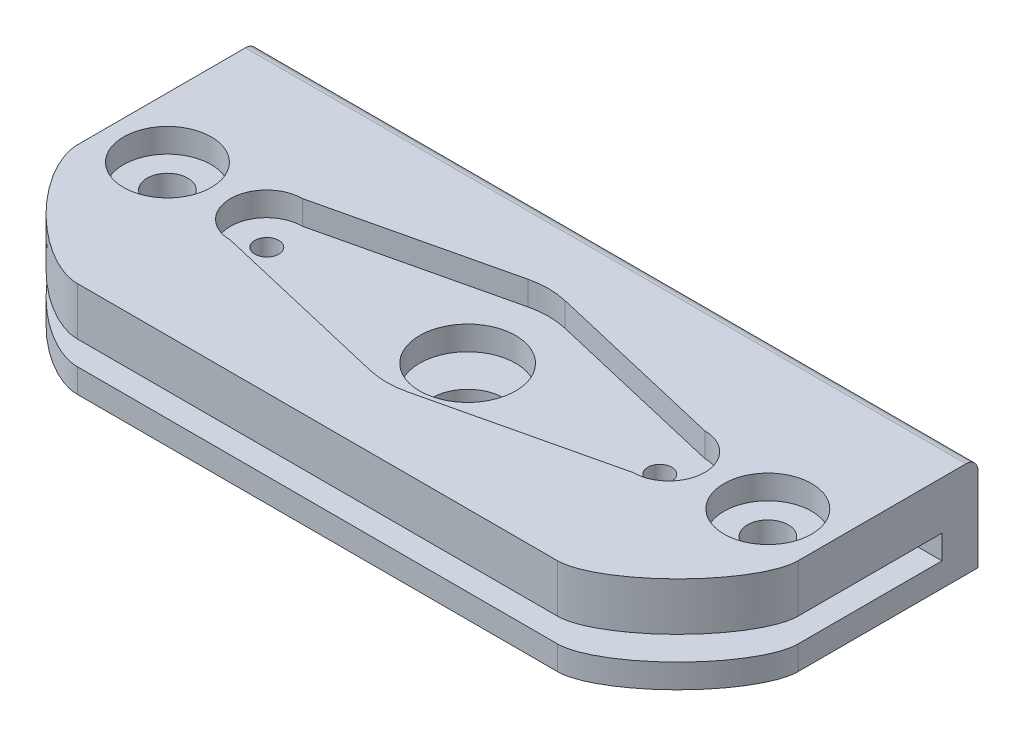
SolidWorks part; units mm, degrees
ref_plane "Front Plane" through (0, 0, 0) normal (0, 0, 1) x (1, 0, 0)
ref_plane "Top Plane" through (0, 0, 0) normal (0, 1, 0) x (1, 0, 0)
ref_plane "Right Plane" through (0, 0, 0) normal (1, 0, 0) x (0, 0, -1)
sketch "Sketch1" plane through (0, 0, 0) normal (0, 0, 1) x (1, 0, 0)
  line L1 (-20.0715, -2.0352) -> (39.9285, -2.0352)
  line L2 (-20.0715, -2.0352) -> (-20.0715, -10.0352)
  line L3 (-20.0715, -10.0352) -> (39.9285, -10.0352)
  line L4 (39.9285, -2.0352) -> (39.9285, -10.0352)
extrude "Boss-Extrude1" add sketch "Sketch1" along normal blind 25
sketch "Sketch2" plane through (0, 0, 25) normal (0, 0, 1) x (1, 0, 0)
  line L0 (-20.0715, -6.0352) -> (-20.0715, -8.0352)
  line L1 (-20.0715, -2.0352) -> (-20.0715, -10.0352) construction
  line L2 (-20.0715, -8.0352) -> (39.9285, -8.0352)
  line L3 (39.9285, -10.0352) -> (39.9285, -2.0352) construction
  line L4 (39.9285, -8.0352) -> (39.9285, -6.0352)
  line L5 (39.9285, -6.0352) -> (-20.0715, -6.0352)
extrude "Cut-Extrude1" cut sketch "Sketch2" against normal blind 22
sketch "Sketch3" plane through (0, -2.0352, 0) normal (0, 1, 0) x (1, 0, 0)
  line L3 (26.6785, -9.5) -> (11.4717, -5.9288)
  line L4 (-6.8215, -9.5) -> (8.3853, -5.9288)
  line L5 (-6.8215, -15.5) -> (8.3853, -19.0712)
  line L6 (26.6785, -15.5) -> (11.4717, -19.0712)
  arc A0 (8.3853, -19.0712) -> (11.4717, -19.0712) centre (9.9285, -12.5) ccw
  arc A1 (-6.8215, -9.5) -> (-6.8215, -15.5) centre (-6.8215, -12.5) ccw
  arc A2 (26.6785, -15.5) -> (26.6785, -9.5) centre (26.6785, -12.5) ccw
  arc A3 (11.4717, -5.9288) -> (8.3853, -5.9288) centre (9.9285, -12.5) ccw
extrude "Cut-Extrude2" cut sketch "Sketch3" against normal blind 2
sketch "Sketch4" plane through (0, -4.0352, 0) normal (0, 1, 0) x (1, 0, 0)
  circle A0 centre (-6.7969, -12.5) radius 1
  circle A2 centre (9.9285, -12.5) radius 4
  circle A3 centre (25.9285, -12.5) radius 1
extrude "Cut-Extrude3" cut sketch "Sketch4" against normal blind 2.5
sketch "Sketch5" plane through (0, -2.0352, 0) normal (0, 1, 0) x (1, 0, 0)
  line L0 (-20.0715, -12.5) -> (-15.0715, -12.5)
  line L1 (-20.0715, -25) -> (-20.0715, 0) construction
  line L2 (-15.0715, -12.5) -> (-15.0715, 0)
  line L3 (39.9285, 0) -> (-20.0715, 0) construction
  line L4 (-15.0715, -12.5) -> (34.9285, -12.5)
  circle A0 centre (34.9285, -12.5) radius 1.7
  circle A1 centre (-15.0715, -12.5) radius 1.7
extrude "Cut-Extrude4" cut sketch "Sketch5" against normal blind 9
fillet "Fillet1" radius 1 1 edges at (9.9285, -2.0352, 0)
fillet "Fillet2" radius 10 4 edges at (-20.0715, -4.0352, 25) (-20.0715, -9.0352, 25) (39.9285, -4.0352, 25) (39.9285, -9.0352, 25)
sketch "Sketch6" plane through (0, -8.0352, 0) normal (0, 1, 0) x (1, 0, 0)
  circle A0 centre (9.9285, -12.5) radius 3
extrude "Cut-Extrude5" cut sketch "Sketch6" against normal blind 4.5
sketch "Sketch7" plane through (0, -10.0352, 0) normal (0, -1, 0) x (-1, 0, 0)
  line L1 (-35.6839, -9.2377) -> (-38.1315, -11.523)
  line L2 (-38.1315, -11.523) -> (-37.3761, -14.7853)
  line L3 (-37.3761, -14.7853) -> (-34.1731, -15.7623)
  line L4 (-34.1731, -15.7623) -> (-31.7256, -13.477)
  line L5 (-31.7256, -13.477) -> (-32.4809, -10.2147)
  line L6 (-32.4809, -10.2147) -> (-35.6839, -9.2377)
  line L7 (12.1057, -10.9453) -> (12.2421, -14.2911)
  line L8 (12.2421, -14.2911) -> (15.208, -15.8458)
  line L9 (15.208, -15.8458) -> (18.0373, -14.0547)
  line L10 (18.0373, -14.0547) -> (17.9008, -10.7089)
  line L11 (17.9008, -10.7089) -> (14.935, -9.1542)
  line L12 (14.935, -9.1542) -> (12.1057, -10.9453)
  circle A0 centre (-34.9285, -12.5) radius 2.9 construction
  circle A1 centre (15.0715, -12.5) radius 2.9 construction
extrude "Cut-Extrude6" cut sketch "Sketch7" against normal blind 1
sketch "Sketch8" plane through (0, -2.0352, 0) normal (0, 1, 0) x (1, 0, 0)
  circle A0 centre (-15.0715, -12.5) radius 3.65
  circle A1 centre (34.9285, -12.5) radius 3.65
extrude "Cut-Extrude7" cut sketch "Sketch8" against normal blind 2
